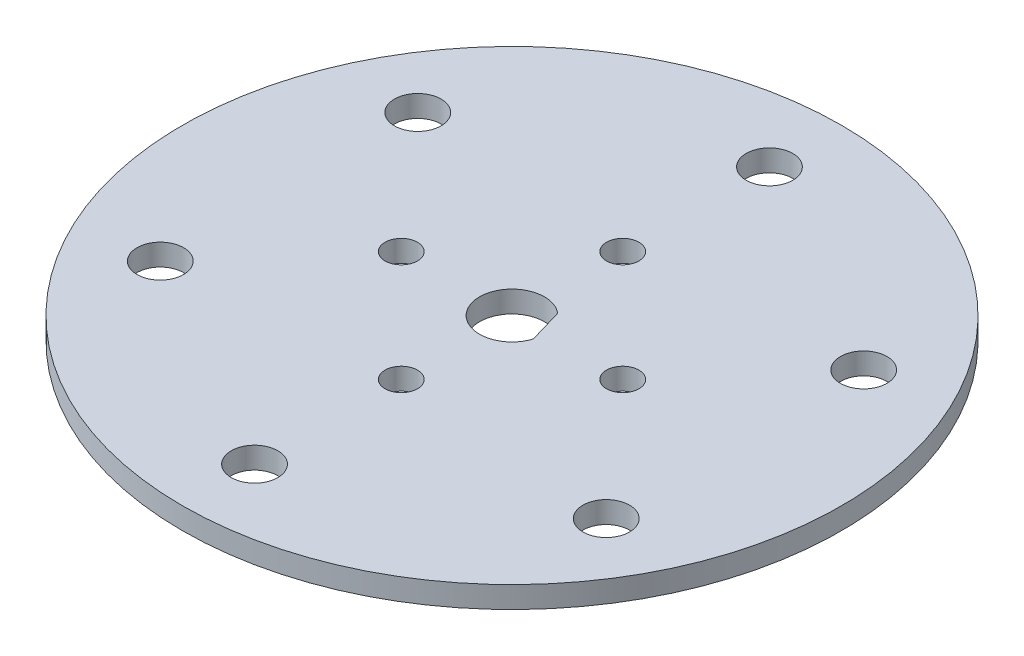
SolidWorks part; units mm, degrees
ref_plane "Front" through (0, 0, 0) normal (0, 0, 1) x (1, 0, 0)
ref_plane "Top" through (0, 0, 0) normal (0, 1, 0) x (1, 0, 0)
ref_plane "Right" through (0, 0, 0) normal (1, 0, 0) x (0, 0, -1)
sketch "Sketch1" plane through (0, 0, 0) normal (0, 1, 0) x (1, 0, 0)
  circle A1 centre (0, 0) radius 30.48
  circle A2 centre (0, -23.8125) radius 2.1526
  circle A3 centre (20.6222, -11.9062) radius 2.1526
  circle A4 centre (20.6222, 11.9063) radius 2.1526
  circle A5 centre (0, 23.8125) radius 2.1526
  circle A6 centre (-20.6222, 11.9062) radius 2.1527
  circle A7 centre (-20.6222, -11.9062) radius 2.1527
  circle A19 centre (-10.2404, 0) radius 1.5
  circle A22 centre (0, 10.2404) radius 1.5
  circle A24 centre (10.2404, 0) radius 1.5
  circle A26 centre (0, -10.2404) radius 1.5
  point P38 (0, 0)
  dimension "D1" = 3
  dimension "D2" = 4
extrude "Boss-Extrude1" add sketch "Sketch1" along normal blind 2
sketch "Sketch2" plane through (0, 2, 0) normal (0, 1, 0) x (1, 0, 0)
  line L0 (2.8645, -0.8913) -> (1.932, 2.295)
  circle A0 centre (0, 0) radius 3
  dimension "D1" = 3.32
extrude "Cut-Extrude1" cut sketch "Sketch2" against normal blind 10 contours L0 A0 region at (-0.1078, 2, 0.0316)
